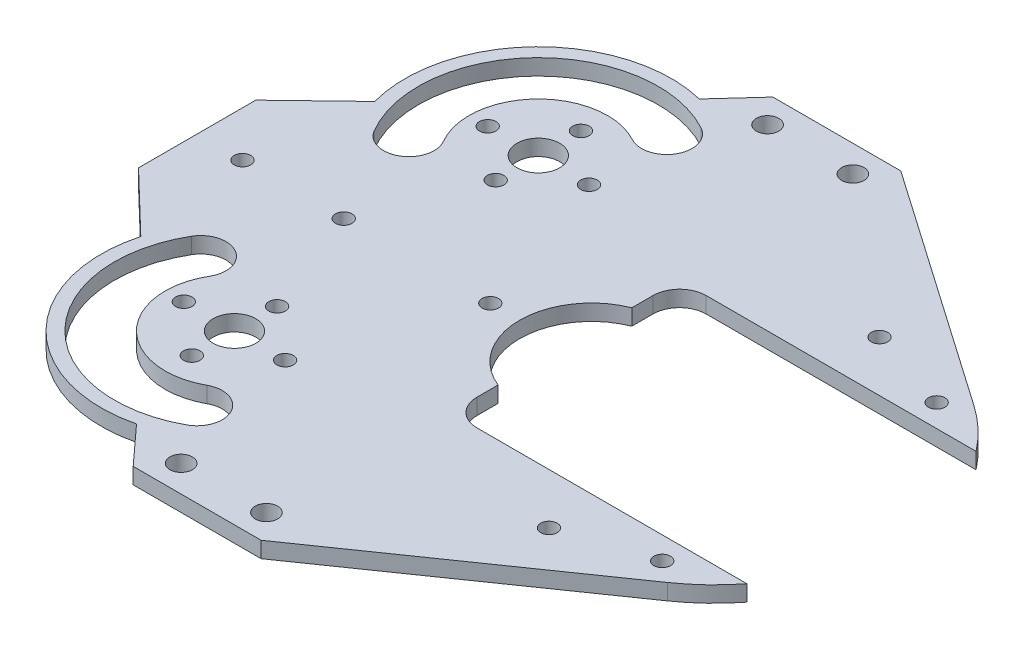
SolidWorks part; units mm, degrees
ref_plane "前视基准面" through (0, 0, 0) normal (0, 0, 1) x (1, 0, 0)
ref_plane "上视基准面" through (0, 0, 0) normal (0, 1, 0) x (1, 0, 0)
ref_plane "右视基准面" through (0, 0, 0) normal (1, 0, 0) x (0, 0, -1)
sketch "草图1" plane through (0, 0, 0) normal (0, 1, 0) x (1, 0, 0)
  line L0 (-55, 11) -> (-55, -11)
  line L1 (-55, 0) -> (5.5, 0) construction
  line L2 (-19.5, 28.5) -> (-19.5, -28.5) construction
  line L3 (-55, -11) -> (-27.8194, -37.148)
  line L4 (28.5, 0) -> (83.1006, 0) construction
  line L5 (-55, 11) -> (-27.8194, 37.148)
  line L6 (14, 12.5399) -> (14, 16.5)
  line L7 (-19.5, 40.5) -> (45.0428, 34.8675)
  line L8 (19, 21.5) -> (69.6179, 21.5)
  line L9 (14, -12.5399) -> (14, -16.5)
  line L13 (19, -21.5) -> (69.6179, -21.5)
  line L15 (-19.5, -40.5) -> (45.0428, -34.8675)
  circle A0 centre (0, 0) radius 1.55
  circle A1 centre (-27.5, 0) radius 1.55
  circle A2 centre (-46.5, 0) radius 1.55
  circle A3 centre (-19.5, -28.5) radius 4
  circle A4 centre (-19.5, -28.5) radius 8 construction
  circle A5 centre (-19.5, -28.5) radius 9.5 construction
  circle A6 centre (-19.5, -20.5) radius 1.55
  circle A7 centre (-19.5, -36.5) radius 1.55
  circle A8 centre (-10, -28.5) radius 1.55
  circle A9 centre (-29, -28.5) radius 1.55
  circle A10 centre (-29, 28.5) radius 1.55
  circle A11 centre (-10, 28.5) radius 1.55
  circle A12 centre (-19.5, 36.5) radius 1.55
  circle A13 centre (-19.5, 20.5) radius 1.55
  circle A14 centre (-19.5, 28.5) radius 4
  arc A15 (-27.8194, -37.148) -> (-17.4214, -40.3186) centre (-19.5, -28.5) ccw
  arc A16 (45.0428, -34.8675) -> (69.6179, -21.5) centre (42, 0) ccw
  arc A17 (-27.8194, 37.148) -> (-17.4214, 40.3186) centre (-19.5, 28.5) cw
  arc A18 (14, 16.5) -> (19, 21.5) centre (19, 16.5) cw
  arc A19 (45.0428, 34.8675) -> (69.6179, 21.5) centre (42, 0) cw
  arc A22 (14, 12.5399) -> (14, -12.5399) centre (19, 0) ccw
  arc A23 (14, -16.5) -> (19, -21.5) centre (19, -16.5) ccw
  point P10 (-55, 0)
  point P15 (-19.5, 0)
  dimension "D1" = 3.1
  dimension "D2" = 3.1
  dimension "D3" = 3.1
  dimension "D9" = 19
  dimension "D10" = 16
  dimension "D11" = 8
  dimension "D12" = 3.1
  dimension "D13" = 3.1
  dimension "D14" = 3.1
  dimension "D15" = 3.1
  dimension "D16" = 24
  dimension "D18" = 70
  dimension "D4" = 27.5
  dimension "D5" = 19
  dimension "D6" = 8.5
  dimension "D7" = 19.5
  dimension "D8" = 57
  dimension "D17" = 22
  dimension "D19" = 42
extrude "凸台-拉伸1" add sketch "草图1" along normal blind 3 contours A23 L9 A22 L6 A18 L8 A19 L7 A17 L5 L0 L3 A15 L15 A16 L13 A13 A11 A0 A1 A2 A3 A6 A7 A8 A9 A10 A12 A14 region at (-3.8495, 0, 0)
sketch "草图2" plane through (0, 3, 0) normal (0, 1, 0) x (1, 0, 0)
  line L0 (0, 0) -> (23.4042, 0) construction
  line L1 (5, 38.3619) -> (5, 57.5706) construction
  line L2 (-16.1256, 50) -> (-7, 50) construction
  line L3 (-7, 60) -> (-28.364, 36.5889)
  line L4 (17, 60) -> (-7, 60)
  line L5 (17, 60) -> (17, 50)
  line L6 (-17.4214, 40.3186) -> (-19.6569, 39.1776)
  line L7 (-19.6569, 39.1776) -> (-24.7059, 39.3119)
  line L8 (17, 60) -> (-7, 50) construction
  line L9 (17, 50) -> (-7, 60) construction
  line L10 (17, 37.3147) -> (17, 50)
  line L11 (-19.5, 40.5) -> (45.0428, 34.8675) construction
  line L12 (-17.4214, 40.3186) -> (17, 37.3147)
  line L13 (-3, 55) -> (13, 55) construction
  arc A1 (-24.7059, 39.3119) -> (-28.364, 36.5889) centre (-19.5, 28.5) ccw
  circle A2 centre (13, 55) radius 2.1
  circle A3 centre (-3, 55) radius 2.1
  point P10 (5, 55)
  dimension "D5" = 4.2
  dimension "D6" = 4.2
  dimension "D9" = 4
  dimension "D1" = 5
  dimension "D3" = 24
  dimension "D4" = 10
extrude "凸台-拉伸3" add sketch "草图2" against normal blind 3
fillet "圆角1" radius 4 1 edges at (17, 1.5, -37.3147)
fillet "圆角2" radius 314 1 edges at (-28.1008, 1.5, -36.8773) type face fillet first side face at (-41.5504, 1.5, -23.9386) second side face at (-17.5504, 1.5, -48.4386)
mirror "镜向2" about plane through (0, 0, 0) normal (0, 0, 1) of "凸台-拉伸3"
fillet "圆角3" radius 314 1 edges at (-28.1008, 1.5, 36.8773) type face fillet first side face at (-41.5504, 1.5, 23.9386) second side face at (-17.5504, 1.5, 48.4386)
fillet "圆角4" radius 4 1 edges at (17, 1.5, 37.3147)
sketch "草图3" plane through (0, 0, 0) normal (0, -1, 0) x (1, 0, 0)
  line L0 (-19.5, 28.5) -> (-10.1874, 19.4294) construction
  arc A1 (-8.6867, 48.2313) -> (-38.9114, 17.1226) centre (-19.5, 28.5) ccw
  arc A8 (-38.9114, 17.1226) -> (-30.7155, 21.9264) centre (-34.8135, 19.5245) ccw
  arc A9 (-13.2523, 39.9003) -> (-8.6867, 48.2313) centre (-10.9695, 44.0658) ccw
  arc A13 (-13.2523, 39.9003) -> (-30.7155, 21.9264) centre (-19.5, 28.5) ccw
  point P16 (-19.5, 28.5)
extrude "切除-拉伸2" cut sketch "草图3" against normal blind 3
sketch "草图4" plane through (0, 0, 0) normal (0, -1, 0) x (1, 0, 0)
  line L0 (-43.6248, 21.943) -> (-41.5357, 23.9528)
  line L1 (-55, 11) -> (-41.5357, 23.9528) construction
  line L2 (-15.5344, 50.6478) -> (-13.5804, 52.7891)
  line L3 (-7, 60) -> (-15.5344, 50.6478) construction
  arc A0 (-25.1183, 40.2233) -> (-31.3671, 33.8077) centre (-19.5, 28.5) ccw
  arc A1 (-15.5344, 50.6478) -> (-41.5357, 23.9528) centre (-19.5, 28.5) ccw
  arc A2 (-13.5804, 52.7891) -> (-43.6248, 21.943) centre (-19.5, 28.5) ccw
  arc A3 (-31.3671, 33.8077) -> (-25.1183, 40.2233) centre (-253.1548, 256.0828) ccw construction
  arc A4 (-31.3671, 33.8077) -> (-25.1183, 40.2233) centre (-253.1548, 256.0828) ccw
  circle A5 centre (-19.5, 28.5) radius 25 construction
  circle A6 centre (-19.5, 28.5) radius 22.5 construction
  dimension "D1" = 2.5
extrude "凸台-拉伸4" add sketch "草图4" against normal blind 3
mirror "镜向9" about plane through (0, 0, 0) normal (0, 0, 1) of "切除-拉伸2", "凸台-拉伸4"
sketch "草图5" plane through (0, 3, 0) normal (0, 1, 0) x (1, 0, 0)
  line L0 (17, 60) -> (61.9756, 28.7398)
  line L1 (0, 0) -> (33.4494, 0) construction
  line L2 (20.6522, 36.996) -> (45.0428, 34.8675) construction
  line L3 (17, 40.9809) -> (17, 60) construction
  line L4 (20.6522, 36.996) -> (45.0428, 34.8675)
  line L5 (17, 40.9809) -> (17, 60)
  line L6 (17, -40.9809) -> (17, -60)
  line L7 (17, -60) -> (61.9756, -28.7398)
  line L8 (20.6522, -36.996) -> (45.0428, -34.8675)
  arc A0 (69.6179, 21.5) -> (45.0428, 34.8675) centre (42, 0) ccw construction
  arc A1 (17, 40.9809) -> (20.6522, 36.996) centre (21, 40.9809) ccw construction
  arc A2 (61.9756, 28.7398) -> (45.0428, 34.8675) centre (42, 0) ccw
  arc A3 (17, 40.9809) -> (20.6522, 36.996) centre (21, 40.9809) ccw
  arc A4 (17, -40.9809) -> (20.6522, -36.996) centre (21, -40.9809) cw
  arc A5 (61.9756, -28.7398) -> (45.0428, -34.8675) centre (42, 0) cw
extrude "凸台-拉伸5" add sketch "草图5" against normal blind 3
sketch "草图6" plane through (0, 0, 0) normal (0, -1, 0) x (1, 0, 0)
  line L0 (61.9755, 28.7398) -> (61.9755, 22.7398)
  circle A0 centre (42, 0) radius 35 construction
  circle A1 centre (57.9755, 25.7398) radius 4 construction
  circle A2 centre (42, 31) radius 4 construction
  circle A3 centre (42, 31) radius 1.55
  circle A4 centre (57.9755, 25.7398) radius 1.55
  point P6 (61.9755, 25.7398)
  dimension "D2" = 70
  dimension "D4" = 8
  dimension "D5" = 8
  dimension "D6" = 3.1
  dimension "D7" = 3.1
  dimension "D1" = 19.9755
  dimension "D3" = 25.7398
extrude "切除-拉伸3" cut sketch "草图6" against normal blind 10 contours A3 | A4
mirror "镜向10" about plane through (0, 0, 0) normal (0, 0, 1) of "切除-拉伸3"
